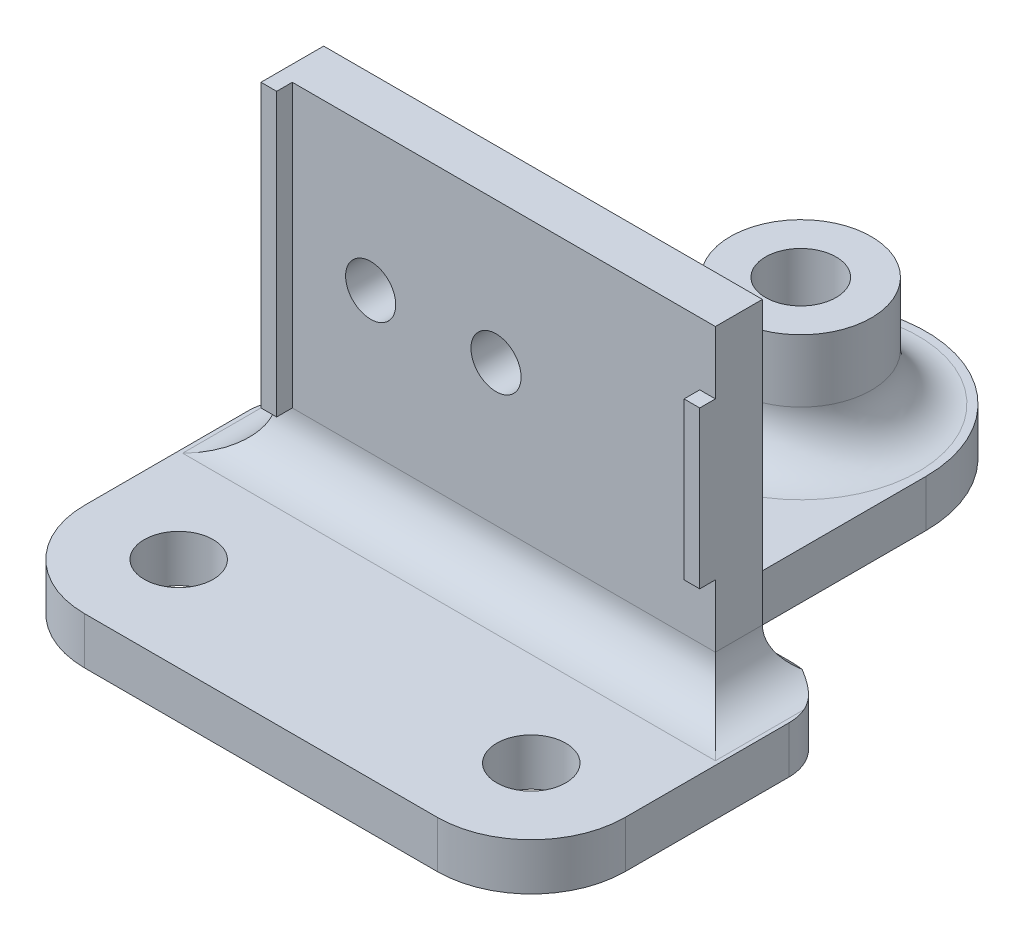
SolidWorks part; units mm, degrees
ref_plane "Front Plane" through (0, 0, 0) normal (0, 0, 1) x (1, 0, 0)
ref_plane "Top Plane" through (0, 0, 0) normal (0, 1, 0) x (1, 0, 0)
ref_plane "Right Plane" through (0, 0, 0) normal (1, 0, 0) x (0, 0, -1)
sketch "Sketch2" plane through (0, 0, 0) normal (0, 1, 0) x (1, 0, 0)
  line L18 (0, 6) -> (0, 16.4501)
  line L33 (3, 19.4501) -> (6.25, 19.4501)
  line L35 (25.25, 34.4501) -> (25.25, 22.4501)
  line L36 (28.25, 19.4501) -> (31.5, 19.4501)
  line L38 (9.25, 34.4501) -> (9.25, 22.4501)
  line L39 (34.5, 6) -> (34.5, 16.4501)
  line L41 (6, 0) -> (28.5, 0)
  circle A0 centre (17.25, 34.4501) radius 2.25
  arc A13 (25.25, 34.4501) -> (9.25, 34.4501) centre (17.25, 34.4501) ccw
  arc A14 (0, 6) -> (6, 0) centre (6, 6) ccw
  arc A15 (28.5, 0) -> (34.5, 6) centre (28.5, 6) ccw
  arc A16 (34.5, 16.4501) -> (31.5, 19.4501) centre (31.5, 16.4501) ccw
  arc A17 (25.25, 22.4501) -> (28.25, 19.4501) centre (28.25, 22.4501) ccw
  arc A18 (6.25, 19.4501) -> (9.25, 22.4501) centre (6.25, 22.4501) ccw
  arc A19 (0, 16.4501) -> (3, 19.4501) centre (3, 16.4501) cw
  circle A20 centre (6, 6) radius 2.2
  circle A21 centre (28.5, 6) radius 2.2
extrude "Boss-Extrude1" add sketch "Sketch2" along normal blind 24
sketch "Sketch3" plane through (0, 24, 0) normal (0, 1, 0) x (1, 0, 0)
  line L26 (4.25, 15) -> (30.25, 15)
  line L27 (30.25, 15) -> (30.25, 14)
  line L28 (30.25, 14) -> (31.25, 14)
  line L29 (4.25, 15) -> (4.25, 14)
  line L30 (4.25, 14) -> (3.25, 14)
  line L37 (3.25, 18) -> (31.25, 18)
  line L42 (3.25, 18) -> (3.25, 14)
  line L43 (31.25, 18) -> (31.25, 14)
  circle A0 centre (17.25, 34.4501) radius 4.5
extrude "Cut-Extrude1" cut sketch "Sketch3" against normal offset from surface (21 mm away) 3 flip side to cut up to face at (17.25, 0, -17.2869)
sketch "Sketch4" plane through (0, 0, -14) normal (0, 0, 1) x (1, 0, 0)
  line L1 (3.25, 3) -> (4.25, 3)
  line L2 (3.25, 3) -> (3.25, 6)
  line L3 (3.25, 6) -> (4.25, 6)
  line L4 (4.25, 3) -> (4.25, 6)
  line L6 (30.25, 3) -> (31.25, 3)
  line L7 (30.25, 3) -> (30.25, 10)
  line L8 (30.25, 10) -> (31.25, 10)
  line L9 (31.25, 3) -> (31.25, 10)
  line L11 (30.25, 24) -> (31.25, 24)
  line L12 (30.25, 24) -> (30.25, 20)
  line L13 (30.25, 20) -> (31.25, 20)
  line L14 (31.25, 24) -> (31.25, 20)
extrude "Cut-Extrude2" cut sketch "Sketch4" against normal up to surface (1 mm away) up to face at (17.25, 13.5, -15)
fillet "Fillet2" radius 3 5 edges at (17.25, 3, -29.9501) (3.25, 3, -16.5) (31.25, 3, -16.5) (17.25, 3, -18) (17.25, 3, -15)
sketch "Sketch6" plane through (0, 0, -15) normal (0, 0, 1) x (1, 0, 0)
  circle A0 centre (9.25, 15) radius 1.6
  circle A1 centre (17.25, 15) radius 1.6
extrude "Cut-Extrude4" cut sketch "Sketch6" against normal up to surface (3 mm away) up to face at (17.25, 15, -18)
sketch "Sketch8" plane through (0, 24, 0) normal (0, 1, 0) x (1, 0, 0)
  circle A0 centre (17.25, 34.4501) radius 4.5
extrude "Cut-Extrude6" cut sketch "Sketch8" against normal offset from surface (14 mm away) 10 up to face at (17.25, 0, -17.2869)
